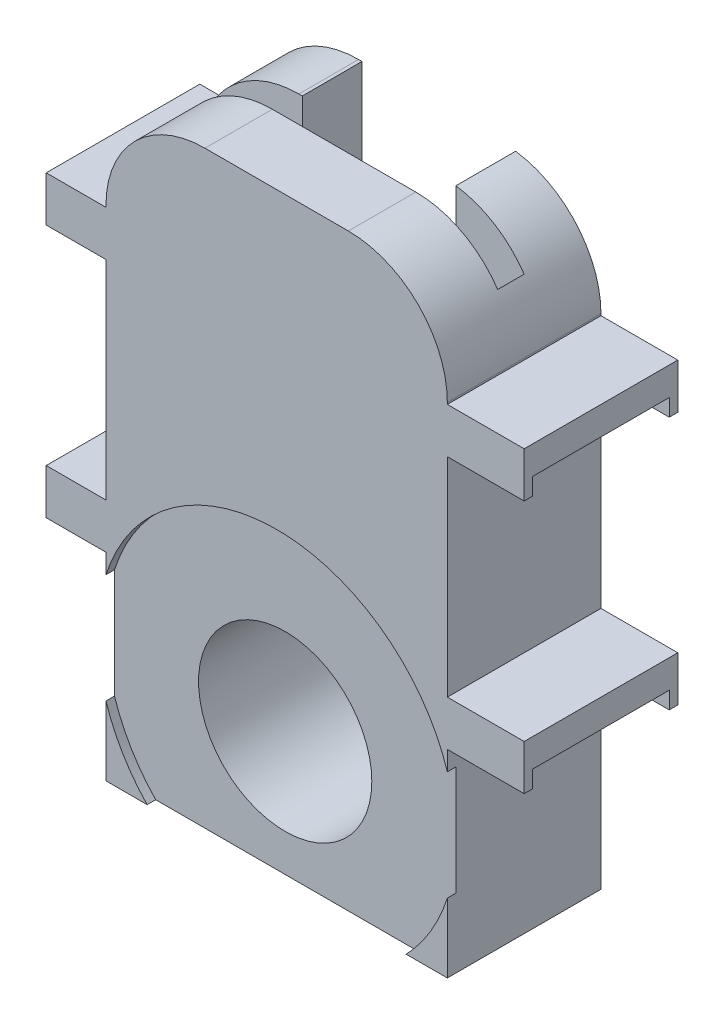
SolidWorks part; units mm, degrees
ref_plane "Front Plane" through (0, 0, 0) normal (0, 0, 1) x (1, 0, 0)
ref_plane "Top Plane" through (0, 0, 0) normal (0, 1, 0) x (1, 0, 0)
ref_plane "Right Plane" through (0, 0, 0) normal (1, 0, 0) x (0, 0, -1)
sketch "Sketch2" plane through (0, 0, 0) normal (0, 0, 1) x (1, 0, 0)
  line L1 (-16.8293, 25.5691) -> (3.1707, 25.5691)
  line L2 (-16.8293, 25.5691) -> (-16.8293, -9.4309)
  line L3 (-16.8293, -9.4309) -> (3.1707, -9.4309)
  line L4 (3.1707, 25.5691) -> (3.1707, -9.4309)
  dimension "D1" = 35
  dimension "D2" = 20
extrude "Boss-Extrude1" add sketch "Sketch2" along normal blind 9
ref_plane "Plane1" through (-6.3293, 0, 0) normal (1, 0, 0) x (0, 0, -1)
sketch "Sketch3" plane through (-6.3293, 0, 0) normal (1, 0, 0) x (0, 0, -1)
  line L0 (-9, -9.4309) -> (-9, 25.5691) construction
  line L1 (-9, 19.6691) -> (0, 19.6691)
  line L2 (-9, 19.6691) -> (-9, 17.0191)
  line L3 (-9, 17.0191) -> (0, 17.0191)
  line L4 (0, 19.6691) -> (0, 17.0191)
  line L5 (0, -9.4309) -> (0, 25.5691) construction
  line L6 (-9, 25.5691) -> (0, 25.5691) construction
  line L7 (-9, 4.8191) -> (0, 4.8191)
  line L8 (-9, 4.8191) -> (-9, 2.1691)
  line L9 (-9, 2.1691) -> (0, 2.1691)
  line L10 (0, 4.8191) -> (0, 2.1691)
  dimension "D1" = 2.65
  dimension "D2" = 2.65
  dimension "D3" = 12.2
  dimension "D4" = 5.9
extrude "Boss-Extrude2" add sketch "Sketch3" along normal blind 14
extrude "Boss-Extrude3" add sketch "Sketch3<2>" against normal blind 14
sketch "Sketch3<2>" plane through (-6.3293, 0, 0) normal (1, 0, 0) x (0, 0, -1) same geometry as "Sketch3"
sketch "Sketch4" plane through (0, 0, 9) normal (0, 0, 1) x (1, 0, 0)
  line L0 (-16.8293, 25.5691) -> (3.1707, 25.5691) construction
  line L1 (-6.8293, 25.5691) -> (-6.8293, -9.4309) construction
  line L2 (-16.8293, -9.4309) -> (3.1707, -9.4309) construction
  circle A0 centre (-6.8293, -2.1737) radius 5.075
extrude "Cut-Extrude1" cut sketch "Sketch4" against normal through all
sketch "Sketch5" plane through (0, 0, 9) normal (0, 0, 1) x (1, 0, 0)
  circle A0 centre (-6.8293, -2.1737) radius 10.5
  dimension "D1" = 21
extrude "Cut-Extrude2" cut sketch "Sketch5" against normal blind 0.5
ref_plane "Plane2" through (-5.2786, 2.3761, 3.675) normal (-0.4018, 0.9157, 0) x (0, 0, -1)
sketch "Sketch7" plane through (0, 25.5691, 0) normal (0, 1, 0) x (1, 0, 0)
  line L0 (-16.8293, -9) -> (-16.8293, 0) construction
  line L1 (-15.8293, -5.05) -> (2.1707, -5.05)
  line L2 (-15.8293, -5.05) -> (-15.8293, -3.5)
  line L3 (-15.8293, -3.5) -> (2.1707, -3.5)
  line L4 (2.1707, -5.05) -> (2.1707, -3.5)
  line L6 (3.1707, 0) -> (-16.8293, 0) construction
  dimension "D3" = 1
  dimension "D1" = 18
  dimension "D2" = 1.55
  dimension "D4" = 3.5
extrude "Cut-Extrude3" cut sketch "Sketch7" against normal blind 22.2
sketch "Sketch8" plane through (0, 25.5691, 0) normal (0, 1, 0) x (1, 0, 0)
  line L0 (2.1707, -3.5) -> (-15.8293, -3.5) construction
  line L1 (-10.8293, -3.5) -> (-1.8293, -3.5)
  line L2 (-10.8293, -3.5) -> (-10.8293, 0)
  line L3 (-10.8293, 0) -> (-1.8293, 0)
  line L4 (-1.8293, -3.5) -> (-1.8293, 0)
  line L5 (3.1707, 0) -> (-16.8293, 0) construction
  line L6 (3.1707, -9) -> (3.1707, 0) construction
  dimension "D1" = 9
  dimension "D2" = 5
extrude "Cut-Extrude4" cut sketch "Sketch8" against normal blind 19
sketch "Sketch9" plane through (0, 2.1691, 0) normal (0, -1, 0) x (1, 0, 0)
  line L0 (-20.3293, 0) -> (-16.8293, 0) construction
  line L1 (-20.3293, 8.5) -> (-17.1293, 8.5)
  line L2 (-20.3293, 8.5) -> (-20.3293, 3.5)
  line L4 (-17.1293, 8.5) -> (-17.1293, 3.5)
  line L14 (-20.3293, 1.5) -> (-20.3293, 0.5)
  line L15 (-20.3293, 0.5) -> (-17.1293, 0.5)
  line L16 (-17.1293, 1.5) -> (-17.1293, 0.5)
  line L17 (-20.3293, 9) -> (-16.8293, 9) construction
  line L19 (-16.8293, 9) -> (-16.8293, 0) construction
  line L20 (3.4707, 8.5) -> (7.6707, 8.5)
  line L21 (3.4707, 8.5) -> (3.4707, 7.5)
  line L23 (7.6707, 8.5) -> (7.6707, 3.5)
  line L24 (3.4707, 7.5) -> (3.4707, 1.5)
  line L25 (7.6707, 3.5) -> (7.6707, 1.5)
  line L27 (-20.3293, 9) -> (-20.3293, 0) construction
  line L30 (3.4707, 1.5) -> (3.4707, 0.5)
  line L31 (3.4707, 0.5) -> (7.6707, 0.5)
  line L32 (7.6707, 1.5) -> (7.6707, 0.5)
  line L34 (3.1707, 9) -> (3.1707, 0) construction
  line L35 (7.6707, 9) -> (3.1707, 9) construction
  line L36 (7.6707, 0) -> (3.1707, 0) construction
  line L37 (-20.3293, 3.5) -> (-20.3293, 1.5)
  line L38 (-17.1293, 3.5) -> (-17.1293, 1.5)
  line L39 (7.6707, 9) -> (7.6707, 0) construction
  dimension "D1" = 0.5
  dimension "D2" = 0.5
  dimension "D8" = 0.3
  dimension "D11" = 1
  dimension "D12" = 1
  dimension "D14" = 0.3
  dimension "D15" = 0.5
  dimension "D16" = 0.5
extrude "Cut-Extrude5" cut sketch "Sketch9" against normal blind 1 contours L4 L1 L2 | L16 L14 L15 | L32 L30 L31 | L23 L25 L32 L31 L30 L24 L21 L20 region at (-18.7293, 2.1691, 4.5) region at (5.5707, 2.1691, 4.5)
sketch "Sketch10" plane through (0, 17.0191, 0) normal (0, -1, 0) x (1, 0, 0)
  line L0 (-20.3293, 9) -> (-20.3293, 8.5) construction
  line L1 (-20.3293, 7) -> (-17.1293, 7)
  line L2 (-20.3293, 7) -> (-20.3293, 0.5)
  line L3 (-20.3293, 0.5) -> (-17.1293, 0.5)
  line L4 (-17.1293, 7) -> (-17.1293, 0.5)
  line L5 (3.4707, 8.5) -> (7.6707, 8.5)
  line L6 (3.4707, 8.5) -> (3.4707, 0.5)
  line L7 (3.4707, 0.5) -> (7.6707, 0.5)
  line L8 (7.6707, 8.5) -> (7.6707, 0.5)
  line L9 (7.6707, 9) -> (7.6707, 8.5) construction
extrude "Cut-Extrude6" cut sketch "Sketch10" against normal blind 1
sketch "Sketch13" plane through (0, 0, 9) normal (0, 0, 1) x (1, 0, 0)
  line L0 (-16.8293, 19.6691) -> (-16.8293, 19.7691)
  line L1 (-11.0293, 25.5691) -> (-2.6293, 25.5691)
  line L2 (3.1707, 19.7691) -> (3.1707, 19.6691)
  line L3 (-16.8293, 19.7691) -> (-16.8293, 25.5691)
  line L4 (-16.8293, 25.5691) -> (-11.0293, 25.5691)
  line L5 (3.1707, 19.7691) -> (3.1707, 25.5691)
  line L6 (3.1707, 25.5691) -> (-2.6293, 25.5691)
  arc A0 (3.1707, 19.7691) -> (-2.6293, 25.5691) centre (-2.6293, 19.7691) ccw
  arc A1 (-11.0293, 25.5691) -> (-16.8293, 19.7691) centre (-11.0293, 19.7691) ccw
  point P10 (3.1707, 25.5691)
  point P13 (-16.8293, 25.5691)
  line M15 (3.1707, 19.6691) -> (3.1707, 25.5691)
  line M16 (3.1707, 25.5691) -> (-16.8293, 25.5691)
  line M17 (-16.8293, 25.5691) -> (-16.8293, 19.6691)
  dimension "D1" = 5.8
extrude "Cut-Extrude7" cut sketch "Sketch13" against normal blind 10 contours A0 M15 M16 | A1 M16 M17 region at (1.8752, 24.2736, 9) region at (-15.5337, 24.2736, 9)
